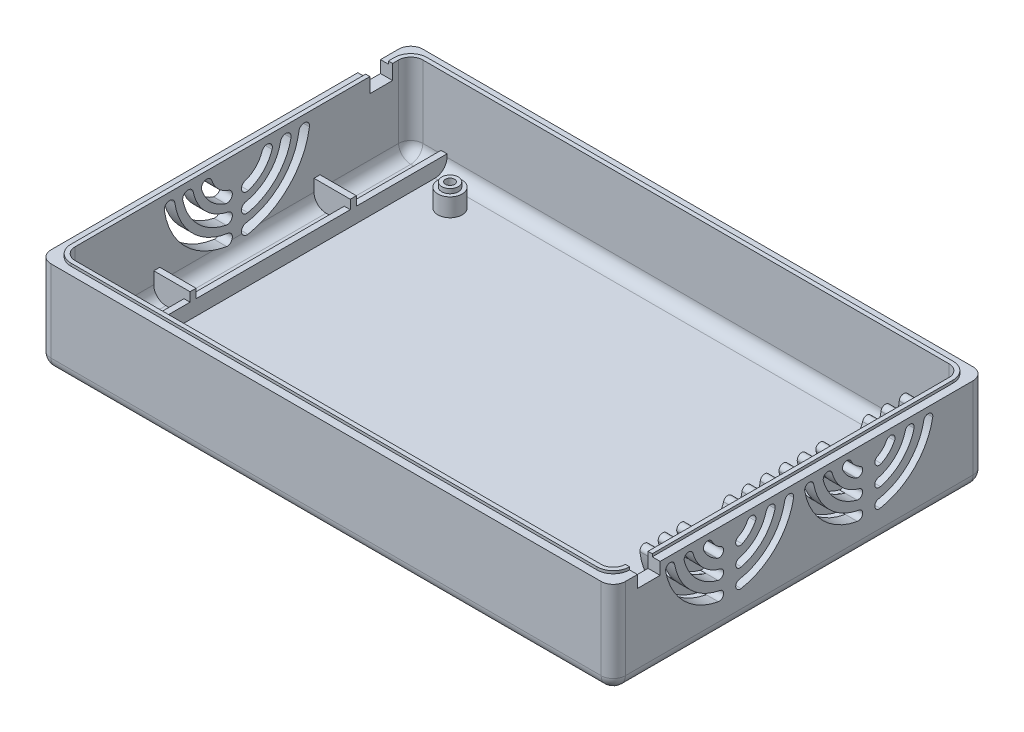
SolidWorks part; units mm, degrees
ref_plane "Front Plane" through (0, 0, 0) normal (0, 0, 1) x (1, 0, 0)
ref_plane "Top Plane" through (0, 0, 0) normal (0, 1, 0) x (1, 0, 0)
ref_plane "Right Plane" through (0, 0, 0) normal (1, 0, 0) x (0, 0, -1)
sketch "Sketch1" plane through (0, 0, 0) normal (0, 1, 0) x (1, 0, 0)
  line L1 (-73.5, -47.5) -> (73.5, -47.5) construction
  line L2 (-73.5, -47.5) -> (-73.5, 47.5) construction
  line L3 (-73.5, 47.5) -> (73.5, 47.5) construction
  line L4 (73.5, -47.5) -> (73.5, 47.5) construction
  line L5 (-73.5, -47.5) -> (73.5, 47.5) construction
  line L6 (-73.5, 47.5) -> (73.5, -47.5) construction
  line L7 (-80.5, -55.5) -> (80.5, -55.5) construction
  line L8 (-80.5, -55.5) -> (-80.5, 55.5) construction
  line L9 (-80.5, 55.5) -> (80.5, 55.5) construction
  line L10 (80.5, -55.5) -> (80.5, 55.5) construction
  line L11 (-80.5, -55.5) -> (80.5, 55.5) construction
  line L12 (-80.5, 55.5) -> (80.5, -55.5) construction
  line L13 (-100.5, 61.5) -> (89.5, 61.5)
  line L14 (-100.5, 61.5) -> (-100.5, -61.5)
  line L15 (-100.5, -61.5) -> (89.5, -61.5)
  line L16 (89.5, 61.5) -> (89.5, -61.5)
  circle A0 centre (73.5, -47.5) radius 1.5
  circle A1 centre (73.5, 47.5) radius 1.5
  circle A2 centre (-73.5, 47.5) radius 1.5
  circle A3 centre (-73.5, -47.5) radius 1.5
  point P0 (0, 0)
  point P6 (0, 0)
  dimension "D9" = 3
  dimension "D1" = 147
  dimension "D2" = 95
  dimension "D3" = 111
  dimension "D4" = 9
  dimension "D5" = 20
  dimension "D6" = 6
  dimension "D7" = 6
  dimension "D8" = 161
extrude "Boss-Extrude1" add sketch "Sketch1" along normal blind 4
sketch "Sketch3" plane through (0, 4, 0) normal (0, 1, 0) x (1, 0, 0)
  circle A0 centre (-73.5, 47.5) radius 4
  circle A1 centre (-73.5, -47.5) radius 4
  circle A2 centre (73.5, -47.5) radius 4
  circle A3 centre (73.5, 47.5) radius 4
  circle A4 centre (-73.5, 47.5) radius 1.5 construction
  circle A5 centre (-73.5, -47.5) radius 1.5 construction
  circle A6 centre (73.5, -47.5) radius 1.5 construction
  circle A7 centre (73.5, 47.5) radius 1.5 construction
  circle A8 centre (-73.5, 47.5) radius 1.5
  circle A9 centre (-73.5, -47.5) radius 1.5
  circle A10 centre (73.5, -47.5) radius 1.5
  circle A11 centre (73.5, 47.5) radius 1.5
  dimension "D1" = 8
extrude "Boss-Extrude3" add sketch "Sketch3" along normal blind 6
sketch "Sketch4" plane through (0, 10, 0) normal (0, 1, 0) x (1, 0, 0)
  circle A0 centre (73.5, -47.5) radius 1.5 construction
  circle A1 centre (73.5, 47.5) radius 1.5 construction
  circle A2 centre (-73.5, 47.5) radius 1.5 construction
  circle A3 centre (-73.5, -47.5) radius 1.5 construction
  circle A4 centre (73.5, -47.5) radius 1.5
  circle A5 centre (73.5, 47.5) radius 1.5
  circle A6 centre (-73.5, 47.5) radius 1.5
  circle A7 centre (-73.5, -47.5) radius 1.5
  circle A8 centre (-73.5, 47.5) radius 2.75
  circle A9 centre (73.5, 47.5) radius 2.75
  circle A10 centre (73.5, -47.5) radius 2.75
  circle A11 centre (-73.5, -47.5) radius 2.75
  dimension "D1" = 5.5
extrude "Boss-Extrude4" add sketch "Sketch4" along normal blind 1.5
sketch "Sketch2" plane through (0, 4, 0) normal (0, 1, 0) x (1, 0, 0)
  line L0 (-96.5, 57.5) -> (-96.5, -57.5)
  line L1 (-96.5, -57.5) -> (85.5, -57.5)
  line L2 (85.5, -57.5) -> (85.5, 57.5)
  line L3 (85.5, 57.5) -> (-96.5, 57.5)
  line L4 (-100.5, 61.5) -> (-100.5, -61.5)
  line L5 (-100.5, -61.5) -> (89.5, -61.5)
  line L6 (89.5, -61.5) -> (89.5, 61.5)
  line L7 (89.5, 61.5) -> (-100.5, 61.5)
  line L8 (-100.5, 61.5) -> (-100.5, -61.5)
  line L9 (-100.5, -61.5) -> (89.5, -61.5)
  line L10 (89.5, -61.5) -> (89.5, 61.5)
  line L11 (89.5, 61.5) -> (-100.5, 61.5)
  dimension "D1" = 0
  dimension "D2" = 4
extrude "Boss-Extrude2" add sketch "Sketch2" along normal blind 27
fillet "Fillet1" radius 4 8 edges at (-96.5, 17.5, 57.5) (-96.5, 17.5, -57.5) (85.5, 17.5, -57.5) (85.5, 17.5, 57.5) (85.5, 4, 0) (-5.5, 4, 57.5) (-96.5, 4, 0) (-5.5, 4, -57.5)
fillet "Fillet2" radius 4 8 edges at (89.5, 15.5, -61.5) (89.5, 0, 0) (89.5, 15.5, 61.5) (-5.5, 0, -61.5) (-100.5, 15.5, -61.5) (-100.5, 15.5, 61.5) (-5.5, 0, 61.5) (-100.5, 0, 0)
sketch "Sketch6" plane through (0, 0, 0) normal (0, -1, 0) x (1, 0, 0)
  circle A0 centre (73.5, 47.5) radius 6
  circle A1 centre (-73.5, 47.5) radius 6
  circle A2 centre (-73.5, -47.5) radius 6
  circle A3 centre (73.5, -47.5) radius 6
  circle A4 centre (73.5, 47.5) radius 1.5 construction
  circle A5 centre (73.5, -47.5) radius 1.5 construction
  circle A6 centre (-73.5, -47.5) radius 1.5 construction
  circle A7 centre (-73.5, 47.5) radius 1.5 construction
  circle A8 centre (73.5, 47.5) radius 1.5
  circle A9 centre (73.5, -47.5) radius 1.5
  circle A10 centre (-73.5, -47.5) radius 1.5
  circle A11 centre (-73.5, 47.5) radius 1.5
  circle A12 centre (-73.5, 47.5) radius 3
  circle A13 centre (73.5, 47.5) radius 3
  circle A14 centre (73.5, -47.5) radius 3
  circle A15 centre (-73.5, -47.5) radius 3
  dimension "D1" = 12
  dimension "D2" = 6
extrude "Boss-Extrude5" add sketch "Sketch6" along normal blind 4 contours A1 A12 | A2 A15 | A3 A14 | A0 A13 region at (67.6697, 0, 47.5) region at (-79.3303, 0, 47.5) region at (-79.3303, 0, -47.5) region at (67.6697, 0, -47.5)
fillet "Fillet3" radius 2 8 edges at (73.5, 0, 53.5) (73.5, 0, -41.5) (-73.5, 0, 53.5) (-73.5, 0, -41.5) (-73.5, -4, -53.5) (-73.5, -4, 41.5) (73.5, -4, 41.5) (73.5, -4, -53.5)
sketch "Sketch7" plane through (0, 4, 0) normal (0, 1, 0) x (1, 0, 0)
  line L0 (81.5, 57.5) -> (-92.5, 57.5) construction
  line L1 (-86.5, 57.5) -> (-84.5, 57.5)
  line L2 (-86.5, 57.5) -> (-86.5, -57.5)
  line L3 (-86.5, -57.5) -> (-84.5, -57.5)
  line L4 (-84.5, 57.5) -> (-84.5, -57.5)
  line L5 (81.5, -57.5) -> (-92.5, -57.5) construction
  line L6 (-96.5, -53.5) -> (-96.5, 53.5) construction
  dimension "D1" = 2
  dimension "D2" = 10
extrude "Boss-Extrude6" add sketch "Sketch7" along normal blind 5
sketch "Sketch8" plane through (0, 31, 0) normal (0, 1, 0) x (1, 0, 0)
  line L0 (-100.5, 57.5) -> (-100.5, -57.5) construction
  line L1 (-100.5, 51.5) -> (-96.5, 51.5)
  line L2 (-100.5, 51.5) -> (-100.5, 44)
  line L3 (-100.5, 44) -> (-96.5, 44)
  line L4 (-96.5, 51.5) -> (-96.5, 44)
  line L5 (-96.5, -53.5) -> (-96.5, 53.5) construction
  line L6 (85.5, 61.5) -> (-96.5, 61.5) construction
  line L7 (85.5, 53.5) -> (85.5, -53.5) construction
  line L8 (85.5, -46) -> (89.5, -46)
  line L9 (85.5, -46) -> (85.5, -53.5)
  line L10 (85.5, -53.5) -> (89.5, -53.5)
  line L11 (89.5, -46) -> (89.5, -53.5)
  line L12 (89.5, -57.5) -> (89.5, 57.5) construction
  line L13 (-96.5, -61.5) -> (85.5, -61.5) construction
  dimension "D1" = 7.5
  dimension "D2" = 10
  dimension "D3" = 8
  dimension "D4" = 7.5
extrude "Cut-Extrude1" cut sketch "Sketch8" against normal blind 4
sketch "Sketch9" plane through (-100.5, 0, 0) normal (-1, 0, 0) x (0, 0, 1)
  line L0 (-25, 31) -> (25, 31) construction
  line L1 (25, 6) -> (-25, 6)
  line L2 (25, 6) -> (25, 56)
  line L3 (25, 56) -> (-25, 56)
  line L4 (-25, 6) -> (-25, 56)
  line L5 (-44, 31) -> (57.5, 31) construction
  line L6 (0, 0) -> (0, 6)
  line L7 (0, 53.5) -> (0, 8.5) construction
  circle A0 centre (0, 31) radius 22.5 construction
  circle A1 centre (0, 31) radius 16.5 construction
  circle A2 centre (0, 31) radius 10.5 construction
  arc A3 (-3.25, 8.736) -> (-22.264, 27.75) centre (0, 31) cw construction
  arc A4 (-23.9957, 27.4972) -> (-3.5028, 7.0043) centre (0, 31) ccw
  arc A5 (-20.5324, 28.0028) -> (-2.9972, 10.4676) centre (0, 31) ccw
  arc A6 (-20.5324, 28.0028) -> (-23.9957, 27.4972) centre (-22.264, 27.75) ccw
  arc A7 (-3.5028, 7.0043) -> (-2.9972, 10.4676) centre (-3.25, 8.736) ccw
  arc A8 (22.264, 27.75) -> (3.25, 8.736) centre (0, 31) cw construction
  arc A9 (3.5028, 7.0043) -> (23.9957, 27.4972) centre (0, 31) ccw
  arc A10 (2.9972, 10.4676) -> (20.5324, 28.0028) centre (0, 31) ccw
  arc A11 (2.9972, 10.4676) -> (3.5028, 7.0043) centre (3.25, 8.736) ccw
  arc A12 (23.9957, 27.4972) -> (20.5324, 28.0028) centre (22.264, 27.75) ccw
  arc A13 (-3.25, 14.8232) -> (-16.1768, 27.75) centre (0, 31) cw construction
  arc A14 (-17.8925, 27.4053) -> (-3.5947, 13.1075) centre (0, 31) ccw
  arc A15 (-14.461, 28.0947) -> (-2.9053, 16.539) centre (0, 31) ccw
  arc A16 (-14.461, 28.0947) -> (-17.8925, 27.4053) centre (-16.1768, 27.75) ccw
  arc A17 (-3.5947, 13.1075) -> (-2.9053, 16.539) centre (-3.25, 14.8232) ccw
  arc A18 (-3.25, 21.0156) -> (-9.9844, 27.75) centre (0, 31) cw construction
  arc A19 (-11.6484, 27.2083) -> (-3.7917, 19.3516) centre (0, 31) ccw
  arc A20 (-8.3203, 28.2917) -> (-2.7083, 22.6797) centre (0, 31) ccw
  arc A21 (-8.3203, 28.2917) -> (-11.6484, 27.2083) centre (-9.9844, 27.75) ccw
  arc A22 (-3.7917, 19.3516) -> (-2.7083, 22.6797) centre (-3.25, 21.0156) ccw
  arc A23 (3.25, 21.0156) -> (9.9844, 27.75) centre (0, 31) ccw construction
  arc A24 (3.7917, 19.3516) -> (11.6484, 27.2083) centre (0, 31) ccw
  arc A25 (2.7083, 22.6797) -> (8.3203, 28.2917) centre (0, 31) ccw
  arc A26 (2.7083, 22.6797) -> (3.7917, 19.3516) centre (3.25, 21.0156) ccw
  arc A27 (11.6484, 27.2083) -> (8.3203, 28.2917) centre (9.9844, 27.75) ccw
  arc A28 (3.25, 14.8232) -> (16.1768, 27.75) centre (0, 31) ccw construction
  arc A29 (3.5947, 13.1075) -> (17.8925, 27.4053) centre (0, 31) ccw
  arc A30 (2.9053, 16.539) -> (14.461, 28.0947) centre (0, 31) ccw
  arc A31 (2.9053, 16.539) -> (3.5947, 13.1075) centre (3.25, 14.8232) ccw
  arc A32 (17.8925, 27.4053) -> (14.461, 28.0947) centre (16.1768, 27.75) ccw
  arc A33 (-3.25, 53.264) -> (-22.264, 34.25) centre (0, 31) ccw construction
  arc A34 (-23.9957, 34.5028) -> (-3.5028, 54.9957) centre (0, 31) cw
  arc A35 (-20.5324, 33.9972) -> (-2.9972, 51.5324) centre (0, 31) cw
  arc A36 (-20.5324, 33.9972) -> (-23.9957, 34.5028) centre (-22.264, 34.25) cw
  arc A37 (-3.5028, 54.9957) -> (-2.9972, 51.5324) centre (-3.25, 53.264) cw
  arc A38 (22.264, 34.25) -> (3.25, 53.264) centre (0, 31) ccw construction
  arc A39 (3.5028, 54.9957) -> (23.9957, 34.5028) centre (0, 31) cw
  arc A40 (2.9972, 51.5324) -> (20.5324, 33.9972) centre (0, 31) cw
  arc A41 (2.9972, 51.5324) -> (3.5028, 54.9957) centre (3.25, 53.264) cw
  arc A42 (23.9957, 34.5028) -> (20.5324, 33.9972) centre (22.264, 34.25) cw
  arc A43 (-3.25, 47.1768) -> (-16.1768, 34.25) centre (0, 31) ccw construction
  arc A44 (-17.8925, 34.5947) -> (-3.5947, 48.8925) centre (0, 31) cw
  arc A45 (-14.461, 33.9053) -> (-2.9053, 45.461) centre (0, 31) cw
  arc A46 (-14.461, 33.9053) -> (-17.8925, 34.5947) centre (-16.1768, 34.25) cw
  arc A47 (-3.5947, 48.8925) -> (-2.9053, 45.461) centre (-3.25, 47.1768) cw
  arc A48 (-3.25, 40.9844) -> (-9.9844, 34.25) centre (0, 31) ccw construction
  arc A49 (-11.6484, 34.7917) -> (-3.7917, 42.6484) centre (0, 31) cw
  arc A50 (-8.3203, 33.7083) -> (-2.7083, 39.3203) centre (0, 31) cw
  arc A51 (-8.3203, 33.7083) -> (-11.6484, 34.7917) centre (-9.9844, 34.25) cw
  arc A52 (-3.7917, 42.6484) -> (-2.7083, 39.3203) centre (-3.25, 40.9844) cw
  arc A53 (3.25, 40.9844) -> (9.9844, 34.25) centre (0, 31) cw construction
  arc A54 (3.7917, 42.6484) -> (11.6484, 34.7917) centre (0, 31) cw
  arc A55 (2.7083, 39.3203) -> (8.3203, 33.7083) centre (0, 31) cw
  arc A56 (2.7083, 39.3203) -> (3.7917, 42.6484) centre (3.25, 40.9844) cw
  arc A57 (11.6484, 34.7917) -> (8.3203, 33.7083) centre (9.9844, 34.25) cw
  arc A58 (3.25, 47.1768) -> (16.1768, 34.25) centre (0, 31) cw construction
  arc A59 (3.5947, 48.8925) -> (17.8925, 34.5947) centre (0, 31) cw
  arc A60 (2.9053, 45.461) -> (14.461, 33.9053) centre (0, 31) cw
  arc A61 (2.9053, 45.461) -> (3.5947, 48.8925) centre (3.25, 47.1768) cw
  arc A62 (17.8925, 34.5947) -> (14.461, 33.9053) centre (16.1768, 34.25) cw
  point P19 (-15.9099, 15.0901)
  point P24 (15.9099, 15.0901)
  point P35 (-11.6673, 19.3327)
  point P43 (-7.4246, 23.5754)
  point P51 (7.4246, 23.5754)
  point P59 (11.6673, 19.3327)
  point P64 (0, 0)
  point P65 (0, 0)
  point P66 (0, 0)
  point P67 (0, 0)
  point P68 (0, 0)
  point P69 (15.5265, 25.4163)
  point P70 (0, 0)
  point P71 (22.2891, 27.6475)
  point P72 (0, 0)
  point P75 (-15.9099, 46.9099)
  point P82 (15.9099, 46.9099)
  point P89 (-11.6673, 42.6673)
  point P96 (-7.4246, 38.4246)
  point P103 (7.4246, 38.4246)
  point P110 (11.6673, 42.6673)
  dimension "D2" = 45
  dimension "D3" = 6
  dimension "D4" = 6
  dimension "D5" = 3.5
  dimension "D6" = 1.5
  dimension "D7" = 1.5
  dimension "D1" = 50
extrude "Cut-Extrude2" cut sketch "Sketch9" against normal blind 10 contours A19 A22 A20 A21 | A14 A17 A15 A16 | A4 A7 A5 A6 | A9 A12 A10 A11 | A24 A27 A25 A26 | A29 A32 A30 A31 region at (-100.5, 29.1666, -22.4708) region at (-100.5, 8.5292, 1.8334) region at (-100.5, 20.1525, -10.8475) region at (-100.5, 23.9632, -7.0368) region at (-100.5, 23.9632, 7.0368)
sketch "Sketch10" plane through (89.5, 0, 0) normal (1, 0, 0) x (0, 0, -1)
  line L0 (-46, 31) -> (57.5, 31) construction
  line L5 (23, 51) -> (23, 11) construction
  line L6 (3, 31) -> (43, 31) construction
  circle A0 centre (23, 31) radius 20 construction
  circle A2 centre (23, 31) radius 14 construction
  arc A3 (3.3086, 27.5) -> (19.5, 11.3086) centre (23, 31) ccw construction
  arc A4 (1.8318, 27.2375) -> (19.2375, 9.8318) centre (23, 31) ccw
  arc A5 (4.7855, 27.7625) -> (19.7625, 12.7855) centre (23, 31) ccw
  arc A6 (4.7855, 27.7625) -> (1.8318, 27.2375) centre (3.3086, 27.5) ccw
  arc A7 (19.2375, 9.8318) -> (19.7625, 12.7855) centre (19.5, 11.3086) ccw
  arc A8 (9.4446, 27.5) -> (19.5, 17.4446) centre (23, 31) ccw construction
  arc A9 (7.9922, 27.125) -> (19.125, 15.9922) centre (23, 31) ccw
  arc A10 (10.8969, 27.875) -> (19.875, 18.8969) centre (23, 31) ccw
  arc A11 (10.8969, 27.875) -> (7.9922, 27.125) centre (9.4446, 27.5) ccw
  arc A12 (19.125, 15.9922) -> (19.875, 18.8969) centre (19.5, 17.4446) ccw
  circle A13 centre (23, 31) radius 8 construction
  arc A14 (19.5, 23.8063) -> (15.8063, 27.5) centre (23, 31) cw construction
  arc A15 (14.4574, 26.8437) -> (18.8437, 22.4574) centre (23, 31) ccw
  arc A16 (17.1551, 28.1562) -> (20.1562, 25.1551) centre (23, 31) ccw
  arc A17 (17.1551, 28.1562) -> (14.4574, 26.8437) centre (15.8063, 27.5) ccw
  arc A18 (18.8437, 22.4574) -> (20.1562, 25.1551) centre (19.5, 23.8063) ccw
  arc A19 (42.6914, 27.5) -> (26.5, 11.3086) centre (23, 31) cw construction
  arc A20 (44.1682, 27.2375) -> (26.7625, 9.8318) centre (23, 31) cw
  arc A21 (41.2145, 27.7625) -> (26.2375, 12.7855) centre (23, 31) cw
  arc A22 (41.2145, 27.7625) -> (44.1682, 27.2375) centre (42.6914, 27.5) cw
  arc A23 (26.7625, 9.8318) -> (26.2375, 12.7855) centre (26.5, 11.3086) cw
  arc A24 (36.5554, 27.5) -> (26.5, 17.4446) centre (23, 31) cw construction
  arc A25 (38.0078, 27.125) -> (26.875, 15.9922) centre (23, 31) cw
  arc A26 (35.1031, 27.875) -> (26.125, 18.8969) centre (23, 31) cw
  arc A27 (35.1031, 27.875) -> (38.0078, 27.125) centre (36.5554, 27.5) cw
  arc A28 (26.875, 15.9922) -> (26.125, 18.8969) centre (26.5, 17.4446) cw
  arc A29 (26.5, 23.8063) -> (30.1937, 27.5) centre (23, 31) ccw construction
  arc A30 (31.5426, 26.8438) -> (27.1563, 22.4574) centre (23, 31) cw
  arc A31 (28.8449, 28.1562) -> (25.8438, 25.1551) centre (23, 31) cw
  arc A32 (28.8449, 28.1562) -> (31.5426, 26.8438) centre (30.1937, 27.5) cw
  arc A33 (27.1563, 22.4574) -> (25.8438, 25.1551) centre (26.5, 23.8063) cw
  arc A34 (3.3086, 34.5) -> (19.5, 50.6914) centre (23, 31) cw construction
  arc A35 (1.8318, 34.7625) -> (19.2375, 52.1682) centre (23, 31) cw
  arc A36 (4.7855, 34.2375) -> (19.7625, 49.2145) centre (23, 31) cw
  arc A37 (4.7855, 34.2375) -> (1.8318, 34.7625) centre (3.3086, 34.5) cw
  arc A38 (19.2375, 52.1682) -> (19.7625, 49.2145) centre (19.5, 50.6914) cw
  arc A39 (9.4446, 34.5) -> (19.5, 44.5554) centre (23, 31) cw construction
  arc A40 (7.9922, 34.875) -> (19.125, 46.0078) centre (23, 31) cw
  arc A41 (10.8969, 34.125) -> (19.875, 43.1031) centre (23, 31) cw
  arc A42 (10.8969, 34.125) -> (7.9922, 34.875) centre (9.4446, 34.5) cw
  arc A43 (19.125, 46.0078) -> (19.875, 43.1031) centre (19.5, 44.5554) cw
  arc A44 (19.5, 38.1937) -> (15.8063, 34.5) centre (23, 31) ccw construction
  arc A45 (14.4574, 35.1563) -> (18.8437, 39.5426) centre (23, 31) cw
  arc A46 (17.1551, 33.8438) -> (20.1562, 36.8449) centre (23, 31) cw
  arc A47 (17.1551, 33.8438) -> (14.4574, 35.1563) centre (15.8063, 34.5) cw
  arc A48 (18.8437, 39.5426) -> (20.1562, 36.8449) centre (19.5, 38.1937) cw
  arc A49 (42.6914, 34.5) -> (26.5, 50.6914) centre (23, 31) ccw construction
  arc A50 (44.1682, 34.7625) -> (26.7625, 52.1682) centre (23, 31) ccw
  arc A51 (41.2145, 34.2375) -> (26.2375, 49.2145) centre (23, 31) ccw
  arc A52 (41.2145, 34.2375) -> (44.1682, 34.7625) centre (42.6914, 34.5) ccw
  arc A53 (26.7625, 52.1682) -> (26.2375, 49.2145) centre (26.5, 50.6914) ccw
  arc A54 (36.5554, 34.5) -> (26.5, 44.5554) centre (23, 31) ccw construction
  arc A55 (38.0078, 34.875) -> (26.875, 46.0078) centre (23, 31) ccw
  arc A56 (35.1031, 34.125) -> (26.125, 43.1031) centre (23, 31) ccw
  arc A57 (35.1031, 34.125) -> (38.0078, 34.875) centre (36.5554, 34.5) ccw
  arc A58 (26.875, 46.0078) -> (26.125, 43.1031) centre (26.5, 44.5554) ccw
  arc A59 (26.5, 38.1937) -> (30.1937, 34.5) centre (23, 31) cw construction
  arc A60 (31.5426, 35.1562) -> (27.1563, 39.5426) centre (23, 31) ccw
  arc A61 (28.8449, 33.8438) -> (25.8438, 36.8449) centre (23, 31) ccw
  arc A62 (28.8449, 33.8438) -> (31.5426, 35.1562) centre (30.1937, 34.5) ccw
  arc A63 (27.1563, 39.5426) -> (25.8438, 36.8449) centre (26.5, 38.1937) ccw
  point P11 (8.8579, 16.8579)
  point P16 (13.1005, 21.1005)
  point P28 (17.3431, 25.3431)
  point P33 (0, 0)
  point P34 (0, 0)
  point P35 (23.9599, 17.8489)
  point P36 (0, 0)
  point P39 (37.1421, 16.8579)
  point P46 (32.8995, 21.1005)
  point P53 (28.6569, 25.3431)
  point P61 (8.8579, 45.1421)
  point P68 (13.1005, 40.8995)
  point P75 (17.3431, 36.6569)
  point P82 (37.1421, 45.1421)
  point P89 (32.8995, 40.8995)
  point P96 (28.6569, 36.6569)
  dimension "D1" = 40
  dimension "D2" = 6
  dimension "D3" = 3
  dimension "D4" = 6
  dimension "D6" = 2
  dimension "D5" = 2
  dimension "D7" = 23
extrude "Cut-Extrude4" cut sketch "Sketch10" against normal blind 10
sketch "Sketch11" plane through (85.5, 0, 0) normal (-1, 0, 0) x (0, 0, 1)
  line L0 (-23, 51) -> (-23, 11) construction
  line L1 (-3, 31) -> (-43, 31) construction
  line L2 (-23, 51) -> (-23, 11) construction
  line L3 (-3, 31) -> (-43, 31) construction
  circle A0 centre (-23, 31) radius 20 construction
  circle A1 centre (-23, 31) radius 14 construction
  circle A2 centre (-23, 31) radius 8 construction
  circle A3 centre (-23, 31) radius 20 construction
  arc A4 (-19.2375, 9.8318) -> (-1.8318, 27.2375) centre (-23, 31) ccw
  arc A5 (-19.7625, 12.7855) -> (-19.2375, 9.8318) centre (-19.5, 11.3086) ccw
  arc A6 (-19.7625, 12.7855) -> (-4.7855, 27.7625) centre (-23, 31) ccw
  arc A7 (-1.8318, 27.2375) -> (-4.7855, 27.7625) centre (-3.3086, 27.5) ccw
  arc A8 (-19.2375, 9.8318) -> (-1.8318, 27.2375) centre (-23, 31) ccw
  arc A9 (-19.7625, 12.7855) -> (-19.2375, 9.8318) centre (-19.5, 11.3086) ccw
  arc A10 (-19.7625, 12.7855) -> (-4.7855, 27.7625) centre (-23, 31) ccw
  arc A11 (-1.8318, 27.2375) -> (-4.7855, 27.7625) centre (-3.3086, 27.5) ccw
  arc A12 (-19.125, 15.9922) -> (-7.9922, 27.125) centre (-23, 31) ccw
  arc A13 (-19.875, 18.8969) -> (-19.125, 15.9922) centre (-19.5, 17.4446) ccw
  arc A14 (-19.875, 18.8969) -> (-10.8969, 27.875) centre (-23, 31) ccw
  arc A15 (-7.9922, 27.125) -> (-10.8969, 27.875) centre (-9.4446, 27.5) ccw
  arc A16 (-19.125, 15.9922) -> (-7.9922, 27.125) centre (-23, 31) ccw
  arc A17 (-19.875, 18.8969) -> (-19.125, 15.9922) centre (-19.5, 17.4446) ccw
  arc A18 (-19.875, 18.8969) -> (-10.8969, 27.875) centre (-23, 31) ccw
  arc A19 (-7.9922, 27.125) -> (-10.8969, 27.875) centre (-9.4446, 27.5) ccw
  arc A20 (-44.1682, 27.2375) -> (-26.7625, 9.8318) centre (-23, 31) ccw
  arc A21 (-26.7625, 9.8318) -> (-26.2375, 12.7855) centre (-26.5, 11.3086) ccw
  arc A22 (-41.2145, 27.7625) -> (-26.2375, 12.7855) centre (-23, 31) ccw
  arc A23 (-41.2145, 27.7625) -> (-44.1682, 27.2375) centre (-42.6914, 27.5) ccw
  arc A24 (-44.1682, 27.2375) -> (-26.7625, 9.8318) centre (-23, 31) ccw
  arc A25 (-26.7625, 9.8318) -> (-26.2375, 12.7855) centre (-26.5, 11.3086) ccw
  arc A26 (-41.2145, 27.7625) -> (-26.2375, 12.7855) centre (-23, 31) ccw
  arc A27 (-41.2145, 27.7625) -> (-44.1682, 27.2375) centre (-42.6914, 27.5) ccw
  arc A28 (-20.1563, 25.1551) -> (-18.8438, 22.4574) centre (-19.5, 23.8063) ccw
  arc A29 (-18.8438, 22.4574) -> (-14.4574, 26.8437) centre (-23, 31) ccw
  arc A30 (-14.4574, 26.8437) -> (-17.1551, 28.1562) centre (-15.8063, 27.5) ccw
  arc A31 (-20.1563, 25.1551) -> (-17.1551, 28.1562) centre (-23, 31) ccw
  arc A32 (-20.1563, 25.1551) -> (-18.8438, 22.4574) centre (-19.5, 23.8063) ccw
  arc A33 (-18.8438, 22.4574) -> (-14.4574, 26.8437) centre (-23, 31) ccw
  arc A34 (-14.4574, 26.8437) -> (-17.1551, 28.1562) centre (-15.8063, 27.5) ccw
  arc A35 (-20.1563, 25.1551) -> (-17.1551, 28.1562) centre (-23, 31) ccw
  arc A36 (-31.5426, 26.8438) -> (-27.1563, 22.4574) centre (-23, 31) ccw
  arc A37 (-27.1563, 22.4574) -> (-25.8438, 25.1551) centre (-26.5, 23.8063) ccw
  arc A38 (-28.8449, 28.1562) -> (-25.8438, 25.1551) centre (-23, 31) ccw
  arc A39 (-28.8449, 28.1562) -> (-31.5426, 26.8438) centre (-30.1937, 27.5) ccw
  arc A40 (-31.5426, 26.8438) -> (-27.1563, 22.4574) centre (-23, 31) ccw
  arc A41 (-27.1563, 22.4574) -> (-25.8438, 25.1551) centre (-26.5, 23.8063) ccw
  arc A42 (-28.8449, 28.1562) -> (-25.8438, 25.1551) centre (-23, 31) ccw
  arc A43 (-28.8449, 28.1562) -> (-31.5426, 26.8438) centre (-30.1937, 27.5) ccw
  arc A44 (-26.875, 15.9922) -> (-26.125, 18.8969) centre (-26.5, 17.4446) ccw
  arc A45 (-35.1031, 27.875) -> (-26.125, 18.8969) centre (-23, 31) ccw
  arc A46 (-35.1031, 27.875) -> (-38.0078, 27.125) centre (-36.5554, 27.5) ccw
  arc A47 (-38.0078, 27.125) -> (-26.875, 15.9922) centre (-23, 31) ccw
  arc A48 (-26.875, 15.9922) -> (-26.125, 18.8969) centre (-26.5, 17.4446) ccw
  arc A49 (-35.1031, 27.875) -> (-26.125, 18.8969) centre (-23, 31) ccw
  arc A50 (-35.1031, 27.875) -> (-38.0078, 27.125) centre (-36.5554, 27.5) ccw
  arc A51 (-38.0078, 27.125) -> (-26.875, 15.9922) centre (-23, 31) ccw
  circle A52 centre (-23, 31) radius 14 construction
  circle A53 centre (-23, 31) radius 8 construction
  arc A54 (-30.7207, 28.9044) -> (-25.0956, 23.2793) centre (-23, 31) ccw construction
  arc A55 (-32.1683, 28.5115) -> (-25.4885, 21.8317) centre (-23, 31) ccw
  arc A56 (-29.273, 29.2973) -> (-24.7027, 24.727) centre (-23, 31) ccw
  arc A57 (-29.273, 29.2973) -> (-32.1683, 28.5115) centre (-30.7207, 28.9044) ccw
  arc A58 (-25.4885, 21.8317) -> (-24.7027, 24.727) centre (-25.0956, 23.2793) ccw
  arc A59 (-36.8521, 28.9704) -> (-25.0296, 17.1479) centre (-23, 31) ccw construction
  arc A60 (-38.3363, 28.7529) -> (-25.2471, 15.6637) centre (-23, 31) ccw
  arc A61 (-35.3679, 29.1878) -> (-24.8122, 18.6321) centre (-23, 31) ccw
  arc A62 (-35.3679, 29.1878) -> (-38.3363, 28.7529) centre (-36.8521, 28.9704) ccw
  arc A63 (-25.2471, 15.6637) -> (-24.8122, 18.6321) centre (-25.0296, 17.1479) ccw
  arc A64 (-42.8983, 28.9857) -> (-25.0143, 11.1017) centre (-23, 31) ccw construction
  arc A65 (-44.3907, 28.8346) -> (-25.1654, 9.6093) centre (-23, 31) ccw
  arc A66 (-41.4059, 29.1367) -> (-24.8633, 12.5941) centre (-23, 31) ccw
  arc A67 (-41.4059, 29.1367) -> (-44.3907, 28.8346) centre (-42.8983, 28.9857) ccw
  arc A68 (-25.1654, 9.6093) -> (-24.8633, 12.5941) centre (-25.0143, 11.1017) ccw
  arc A69 (-15.2793, 28.9044) -> (-20.9044, 23.2793) centre (-23, 31) cw construction
  arc A70 (-13.8317, 28.5115) -> (-20.5115, 21.8317) centre (-23, 31) cw
  arc A71 (-16.727, 29.2973) -> (-21.2973, 24.727) centre (-23, 31) cw
  arc A72 (-16.727, 29.2973) -> (-13.8317, 28.5115) centre (-15.2793, 28.9044) cw
  arc A73 (-20.5115, 21.8317) -> (-21.2973, 24.727) centre (-20.9044, 23.2793) cw
  arc A74 (-9.1479, 28.9704) -> (-20.9704, 17.1479) centre (-23, 31) cw construction
  arc A75 (-7.6637, 28.7529) -> (-20.7529, 15.6637) centre (-23, 31) cw
  arc A76 (-10.6321, 29.1878) -> (-21.1878, 18.6321) centre (-23, 31) cw
  arc A77 (-10.6321, 29.1878) -> (-7.6637, 28.7529) centre (-9.1479, 28.9704) cw
  arc A78 (-20.7529, 15.6637) -> (-21.1878, 18.6321) centre (-20.9704, 17.1479) cw
  arc A79 (-3.1017, 28.9857) -> (-20.9857, 11.1017) centre (-23, 31) cw construction
  arc A80 (-1.6093, 28.8346) -> (-20.8346, 9.6093) centre (-23, 31) cw
  arc A81 (-4.5941, 29.1367) -> (-21.1367, 12.5941) centre (-23, 31) cw
  arc A82 (-4.5941, 29.1367) -> (-1.6093, 28.8346) centre (-3.1017, 28.9857) cw
  arc A83 (-20.8346, 9.6093) -> (-21.1367, 12.5941) centre (-20.9857, 11.1017) cw
  arc A84 (-7.9922, 27.125) -> (-19.125, 15.9922) centre (-23, 31) cw
  arc A85 (-10.8969, 27.875) -> (-7.9922, 27.125) centre (-9.4446, 27.5) cw
  arc A86 (-10.8969, 27.875) -> (-19.875, 18.8969) centre (-23, 31) cw
  arc A87 (-19.125, 15.9922) -> (-19.875, 18.8969) centre (-19.5, 17.4446) cw
  arc A88 (-17.1551, 28.1562) -> (-14.4574, 26.8437) centre (-15.8063, 27.5) cw
  arc A89 (-17.1551, 28.1562) -> (-20.1563, 25.1551) centre (-23, 31) cw
  arc A90 (-18.8438, 22.4574) -> (-20.1563, 25.1551) centre (-19.5, 23.8063) cw
  arc A91 (-14.4574, 26.8437) -> (-18.8438, 22.4574) centre (-23, 31) cw
  arc A92 (-4.7855, 27.7625) -> (-1.8318, 27.2375) centre (-3.3086, 27.5) cw
  arc A93 (-4.7855, 27.7625) -> (-19.7625, 12.7855) centre (-23, 31) cw
  arc A94 (-19.2375, 9.8318) -> (-19.7625, 12.7855) centre (-19.5, 11.3086) cw
  arc A95 (-1.8318, 27.2375) -> (-19.2375, 9.8318) centre (-23, 31) cw
  arc A96 (-30.7207, 33.0956) -> (-25.0956, 38.7207) centre (-23, 31) cw construction
  arc A97 (-32.1683, 33.4885) -> (-25.4885, 40.1683) centre (-23, 31) cw
  arc A98 (-29.273, 32.7027) -> (-24.7027, 37.273) centre (-23, 31) cw
  arc A99 (-29.273, 32.7027) -> (-32.1683, 33.4885) centre (-30.7207, 33.0956) cw
  arc A100 (-25.4885, 40.1683) -> (-24.7027, 37.273) centre (-25.0956, 38.7207) cw
  arc A101 (-36.8521, 33.0296) -> (-25.0296, 44.8521) centre (-23, 31) cw construction
  arc A102 (-38.3363, 33.2471) -> (-25.2471, 46.3363) centre (-23, 31) cw
  arc A103 (-35.3679, 32.8122) -> (-24.8122, 43.3679) centre (-23, 31) cw
  arc A104 (-35.3679, 32.8122) -> (-38.3363, 33.2471) centre (-36.8521, 33.0296) cw
  arc A105 (-25.2471, 46.3363) -> (-24.8122, 43.3679) centre (-25.0296, 44.8521) cw
  arc A106 (-42.8983, 33.0143) -> (-25.0143, 50.8983) centre (-23, 31) cw construction
  arc A107 (-44.3907, 33.1654) -> (-25.1654, 52.3907) centre (-23, 31) cw
  arc A108 (-41.4059, 32.8633) -> (-24.8633, 49.4059) centre (-23, 31) cw
  arc A109 (-41.4059, 32.8633) -> (-44.3907, 33.1654) centre (-42.8983, 33.0143) cw
  arc A110 (-25.1654, 52.3907) -> (-24.8633, 49.4059) centre (-25.0143, 50.8983) cw
  arc A111 (-15.2793, 33.0956) -> (-20.9044, 38.7207) centre (-23, 31) ccw construction
  arc A112 (-13.8317, 33.4885) -> (-20.5115, 40.1683) centre (-23, 31) ccw
  arc A113 (-16.727, 32.7027) -> (-21.2973, 37.273) centre (-23, 31) ccw
  arc A114 (-16.727, 32.7027) -> (-13.8317, 33.4885) centre (-15.2793, 33.0956) ccw
  arc A115 (-20.5115, 40.1683) -> (-21.2973, 37.273) centre (-20.9044, 38.7207) ccw
  arc A116 (-9.1479, 33.0296) -> (-20.9704, 44.8521) centre (-23, 31) ccw construction
  arc A117 (-7.6637, 33.2471) -> (-20.7529, 46.3363) centre (-23, 31) ccw
  arc A118 (-10.6321, 32.8122) -> (-21.1878, 43.3679) centre (-23, 31) ccw
  arc A119 (-10.6321, 32.8122) -> (-7.6637, 33.2471) centre (-9.1479, 33.0296) ccw
  arc A120 (-20.7529, 46.3363) -> (-21.1878, 43.3679) centre (-20.9704, 44.8521) ccw
  arc A121 (-3.1017, 33.0143) -> (-20.9857, 50.8983) centre (-23, 31) ccw construction
  arc A122 (-1.6093, 33.1654) -> (-20.8346, 52.3907) centre (-23, 31) ccw
  arc A123 (-4.5941, 32.8633) -> (-21.1367, 49.4059) centre (-23, 31) ccw
  arc A124 (-4.5941, 32.8633) -> (-1.6093, 33.1654) centre (-3.1017, 33.0143) ccw
  arc A125 (-20.8346, 52.3907) -> (-21.1367, 49.4059) centre (-20.9857, 50.8983) ccw
  arc A126 (-1.8318, 34.7625) -> (-19.2375, 52.1682) centre (-23, 31) ccw
  arc A127 (-19.2375, 52.1682) -> (-19.7625, 49.2145) centre (-19.5, 50.6914) ccw
  arc A128 (-4.7855, 34.2375) -> (-19.7625, 49.2145) centre (-23, 31) ccw
  arc A129 (-4.7855, 34.2375) -> (-1.8318, 34.7625) centre (-3.3086, 34.5) ccw
  arc A130 (-14.4574, 35.1563) -> (-18.8438, 39.5426) centre (-23, 31) ccw
  arc A131 (-18.8438, 39.5426) -> (-20.1563, 36.8449) centre (-19.5, 38.1937) ccw
  arc A132 (-17.1551, 33.8438) -> (-20.1563, 36.8449) centre (-23, 31) ccw
  arc A133 (-17.1551, 33.8438) -> (-14.4574, 35.1563) centre (-15.8063, 34.5) ccw
  arc A134 (-19.125, 46.0078) -> (-19.875, 43.1031) centre (-19.5, 44.5554) ccw
  arc A135 (-10.8969, 34.125) -> (-19.875, 43.1031) centre (-23, 31) ccw
  arc A136 (-10.8969, 34.125) -> (-7.9922, 34.875) centre (-9.4446, 34.5) ccw
  arc A137 (-7.9922, 34.875) -> (-19.125, 46.0078) centre (-23, 31) ccw
  arc A138 (-38.0078, 34.875) -> (-26.875, 46.0078) centre (-23, 31) cw
  arc A139 (-35.1031, 34.125) -> (-38.0078, 34.875) centre (-36.5554, 34.5) cw
  arc A140 (-35.1031, 34.125) -> (-26.125, 43.1031) centre (-23, 31) cw
  arc A141 (-26.875, 46.0078) -> (-26.125, 43.1031) centre (-26.5, 44.5554) cw
  arc A142 (-28.8449, 33.8438) -> (-31.5426, 35.1562) centre (-30.1937, 34.5) cw
  arc A143 (-28.8449, 33.8438) -> (-25.8438, 36.8449) centre (-23, 31) cw
  arc A144 (-27.1563, 39.5426) -> (-25.8438, 36.8449) centre (-26.5, 38.1937) cw
  arc A145 (-31.5426, 35.1562) -> (-27.1563, 39.5426) centre (-23, 31) cw
  arc A146 (-20.1563, 36.8449) -> (-17.1551, 33.8438) centre (-23, 31) cw
  arc A147 (-14.4574, 35.1563) -> (-17.1551, 33.8438) centre (-15.8063, 34.5) cw
  arc A148 (-18.8438, 39.5426) -> (-14.4574, 35.1563) centre (-23, 31) cw
  arc A149 (-20.1563, 36.8449) -> (-18.8438, 39.5426) centre (-19.5, 38.1937) cw
  arc A150 (-41.2145, 34.2375) -> (-44.1682, 34.7625) centre (-42.6914, 34.5) cw
  arc A151 (-41.2145, 34.2375) -> (-26.2375, 49.2145) centre (-23, 31) cw
  arc A152 (-26.7625, 52.1682) -> (-26.2375, 49.2145) centre (-26.5, 50.6914) cw
  arc A153 (-44.1682, 34.7625) -> (-26.7625, 52.1682) centre (-23, 31) cw
  arc A154 (-7.9922, 34.875) -> (-10.8969, 34.125) centre (-9.4446, 34.5) cw
  arc A155 (-19.875, 43.1031) -> (-10.8969, 34.125) centre (-23, 31) cw
  arc A156 (-19.875, 43.1031) -> (-19.125, 46.0078) centre (-19.5, 44.5554) cw
  arc A157 (-19.125, 46.0078) -> (-7.9922, 34.875) centre (-23, 31) cw
  arc A158 (-1.8318, 34.7625) -> (-4.7855, 34.2375) centre (-3.3086, 34.5) cw
  arc A159 (-19.7625, 49.2145) -> (-4.7855, 34.2375) centre (-23, 31) cw
  arc A160 (-19.7625, 49.2145) -> (-19.2375, 52.1682) centre (-19.5, 50.6914) cw
  arc A161 (-19.2375, 52.1682) -> (-1.8318, 34.7625) centre (-23, 31) cw
  point P60 (-28.6569, 25.3431)
  point P67 (-32.8995, 21.1005)
  point P74 (-37.1421, 16.8579)
  point P81 (-17.3431, 25.3431)
  point P88 (-13.1005, 21.1005)
  point P95 (-8.8579, 16.8579)
  point P102 (-28.6569, 36.6569)
  point P109 (-32.8995, 40.8995)
  point P116 (-37.1421, 45.1421)
  point P123 (-17.3431, 36.6569)
  point P130 (-13.1005, 40.8995)
  point P137 (-8.8579, 45.1421)
  arc M30 (-17.1551, 28.1562) -> (-14.4574, 26.8437) centre (-15.8063, 27.5) cw
  arc M32 (-18.8438, 22.4574) -> (-20.1563, 25.1551) centre (-19.5, 23.8063) cw
  arc M34 (-10.8969, 27.875) -> (-7.9922, 27.125) centre (-9.4446, 27.5) cw
  arc M36 (-19.125, 15.9922) -> (-19.875, 18.8969) centre (-19.5, 17.4446) cw
  arc M38 (-38.0078, 27.125) -> (-35.1031, 27.875) centre (-36.5554, 27.5) cw
  arc M40 (-26.125, 18.8969) -> (-26.875, 15.9922) centre (-26.5, 17.4446) cw
  arc M42 (-44.1682, 27.2375) -> (-41.2145, 27.7625) centre (-42.6914, 27.5) cw
  arc M44 (-26.2375, 12.7855) -> (-26.7625, 9.8318) centre (-26.5, 11.3086) cw
  arc M46 (-31.5426, 26.8438) -> (-28.8449, 28.1562) centre (-30.1937, 27.5) cw
  arc M48 (-25.8438, 25.1551) -> (-27.1563, 22.4574) centre (-26.5, 23.8063) cw
  arc M50 (-4.7855, 27.7625) -> (-1.8318, 27.2375) centre (-3.3086, 27.5) cw
  arc M52 (-19.2375, 9.8318) -> (-19.7625, 12.7855) centre (-19.5, 11.3086) cw
  dimension "D1" = 0
  dimension "D2" = 0
  dimension "D3" = 0
  dimension "D4" = 0
  dimension "D5" = 0
  dimension "D6" = 0
extrude "Boss-Extrude8" add sketch "Sketch11" along normal blind 1.8 contours A66 A67 A65 M42 | A61 A62 A60 M38 | A56 A57 A55 M46 | A55 A58 A56 M48 | A60 A63 A61 M40 | A65 A68 A66 M44 | A83 A80 A81 M52 | A78 A75 A76 M36 | A73 A70 A71 M32 | A72 A71 A70 M30 | A77 A76 A75 M34 | A82 A81 A80 M50 region at (85.5, 11.0334, -21.4081) region at (85.5, 29.4081, -3.0334) region at (85.5, 17.0502, -21.3868) region at (85.5, 29.3868, -9.0502) region at (85.5, 29.4081, -42.9666) region at (85.5, 11.0334, -24.5919) region at (85.5, 23.1076, -21.2954) region at (85.5, 29.2954, -15.1076) region at (85.5, 29.2954, -30.8924) region at (85.5, 23.1076, -24.7046) region at (85.5, 17.0502, -24.6132) region at (85.5, 29.3868, -36.9498)
sketch "Sketch12" plane through (83.7, 0, 0) normal (-1, 0, 0) x (0, 0, 1)
  line L0 (-44, 31) -> (57.5, 31) construction
  arc A0 (-19.875, 18.8969) -> (-10.8969, 27.875) centre (-23, 31) ccw construction
  arc A1 (-7.9922, 27.125) -> (-10.8969, 27.875) centre (-9.4446, 27.5) ccw construction
  arc A2 (-7.9922, 27.125) -> (-10.8969, 27.875) centre (-9.4446, 27.5) ccw construction
  arc A3 (-19.875, 18.8969) -> (-10.8969, 27.875) centre (-23, 31) ccw construction
  arc A4 (-19.875, 18.8969) -> (-19.125, 15.9922) centre (-19.5, 17.4446) ccw construction
  arc A5 (-19.875, 18.8969) -> (-19.125, 15.9922) centre (-19.5, 17.4446) ccw construction
  arc A6 (-19.125, 15.9922) -> (-7.9922, 27.125) centre (-23, 31) ccw construction
  arc A7 (-19.125, 15.9922) -> (-7.9922, 27.125) centre (-23, 31) ccw construction
  arc A8 (-19.7625, 12.7855) -> (-4.7855, 27.7625) centre (-23, 31) ccw construction
  arc A9 (-1.8318, 27.2375) -> (-4.7855, 27.7625) centre (-3.3086, 27.5) ccw construction
  arc A10 (-1.8318, 27.2375) -> (-4.7855, 27.7625) centre (-3.3086, 27.5) ccw construction
  arc A11 (-19.7625, 12.7855) -> (-4.7855, 27.7625) centre (-23, 31) ccw construction
  arc A12 (-19.7625, 12.7855) -> (-19.2375, 9.8318) centre (-19.5, 11.3086) ccw construction
  arc A13 (-19.7625, 12.7855) -> (-19.2375, 9.8318) centre (-19.5, 11.3086) ccw construction
  arc A14 (-19.2375, 9.8318) -> (-1.8318, 27.2375) centre (-23, 31) ccw construction
  arc A15 (-19.2375, 9.8318) -> (-1.8318, 27.2375) centre (-23, 31) ccw construction
  arc A16 (-14.4574, 26.8437) -> (-17.1551, 28.1562) centre (-15.8063, 27.5) ccw construction
  arc A17 (-20.1563, 25.1551) -> (-17.1551, 28.1562) centre (-23, 31) ccw construction
  arc A18 (-14.4574, 26.8437) -> (-17.1551, 28.1562) centre (-15.8063, 27.5) ccw construction
  arc A19 (-20.1563, 25.1551) -> (-17.1551, 28.1562) centre (-23, 31) ccw construction
  arc A20 (-18.8438, 22.4574) -> (-14.4574, 26.8437) centre (-23, 31) ccw construction
  arc A21 (-18.8438, 22.4574) -> (-14.4574, 26.8437) centre (-23, 31) ccw construction
  arc A22 (-20.1563, 25.1551) -> (-18.8438, 22.4574) centre (-19.5, 23.8063) ccw construction
  arc A23 (-20.1563, 25.1551) -> (-18.8438, 22.4574) centre (-19.5, 23.8063) ccw construction
  arc A24 (-26.7625, 9.8318) -> (-26.2375, 12.7855) centre (-26.5, 11.3086) ccw construction
  arc A25 (-41.2145, 27.7625) -> (-26.2375, 12.7855) centre (-23, 31) ccw construction
  arc A26 (-41.2145, 27.7625) -> (-44.1682, 27.2375) centre (-42.6914, 27.5) ccw construction
  arc A27 (-44.1682, 27.2375) -> (-26.7625, 9.8318) centre (-23, 31) ccw construction
  arc A28 (-26.875, 15.9922) -> (-26.125, 18.8969) centre (-26.5, 17.4446) ccw construction
  arc A29 (-35.1031, 27.875) -> (-26.125, 18.8969) centre (-23, 31) ccw construction
  arc A30 (-35.1031, 27.875) -> (-38.0078, 27.125) centre (-36.5554, 27.5) ccw construction
  arc A31 (-38.0078, 27.125) -> (-26.875, 15.9922) centre (-23, 31) ccw construction
  arc A32 (-27.1563, 22.4574) -> (-25.8438, 25.1551) centre (-26.5, 23.8063) ccw construction
  arc A33 (-28.8449, 28.1562) -> (-25.8438, 25.1551) centre (-23, 31) ccw construction
  arc A34 (-28.8449, 28.1562) -> (-31.5426, 26.8438) centre (-30.1937, 27.5) ccw construction
  arc A35 (-31.5426, 26.8438) -> (-27.1563, 22.4574) centre (-23, 31) ccw construction
  arc A36 (-44.3907, 28.8346) -> (-25.1654, 9.6093) centre (-23, 31) ccw construction
  arc A37 (-25.1654, 9.6093) -> (-24.8633, 12.5941) centre (-25.0143, 11.1017) ccw construction
  arc A38 (-41.4059, 29.1367) -> (-24.8633, 12.5941) centre (-23, 31) ccw construction
  arc A39 (-41.4059, 29.1367) -> (-44.3907, 28.8346) centre (-42.8983, 28.9857) ccw construction
  arc A40 (-38.3363, 28.7529) -> (-25.2471, 15.6637) centre (-23, 31) ccw construction
  arc A41 (-25.2471, 15.6637) -> (-24.8122, 18.6321) centre (-25.0296, 17.1479) ccw construction
  arc A42 (-35.3679, 29.1878) -> (-24.8122, 18.6321) centre (-23, 31) ccw construction
  arc A43 (-35.3679, 29.1878) -> (-38.3363, 28.7529) centre (-36.8521, 28.9704) ccw construction
  arc A44 (-25.4885, 21.8317) -> (-24.7027, 24.727) centre (-25.0956, 23.2793) ccw construction
  arc A45 (-32.1683, 28.5115) -> (-25.4885, 21.8317) centre (-23, 31) ccw construction
  arc A46 (-29.273, 29.2973) -> (-32.1683, 28.5115) centre (-30.7207, 28.9044) ccw construction
  arc A47 (-29.273, 29.2973) -> (-24.7027, 24.727) centre (-23, 31) ccw construction
  arc A48 (-20.7529, 15.6637) -> (-7.6637, 28.7529) centre (-23, 31) ccw construction
  arc A49 (-21.1878, 18.6321) -> (-20.7529, 15.6637) centre (-20.9704, 17.1479) ccw construction
  arc A50 (-21.1878, 18.6321) -> (-10.6321, 29.1878) centre (-23, 31) ccw construction
  arc A51 (-7.6637, 28.7529) -> (-10.6321, 29.1878) centre (-9.1479, 28.9704) ccw construction
  arc A52 (-20.5115, 21.8317) -> (-13.8317, 28.5115) centre (-23, 31) ccw construction
  arc A53 (-21.2973, 24.727) -> (-20.5115, 21.8317) centre (-20.9044, 23.2793) ccw construction
  arc A54 (-21.2973, 24.727) -> (-16.727, 29.2973) centre (-23, 31) ccw construction
  arc A55 (-13.8317, 28.5115) -> (-16.727, 29.2973) centre (-15.2793, 28.9044) ccw construction
  arc A56 (-20.8346, 9.6093) -> (-1.6093, 28.8346) centre (-23, 31) ccw construction
  arc A57 (-21.1367, 12.5941) -> (-20.8346, 9.6093) centre (-20.9857, 11.1017) ccw construction
  arc A58 (-21.1367, 12.5941) -> (-4.5941, 29.1367) centre (-23, 31) ccw construction
  arc A59 (-1.6093, 28.8346) -> (-4.5941, 29.1367) centre (-3.1017, 28.9857) ccw construction
  arc A60 (-19.875, 18.8969) -> (-10.8969, 27.875) centre (-23, 31) ccw
  arc A61 (-7.9922, 27.125) -> (-10.8969, 27.875) centre (-9.4446, 27.5) ccw construction
  arc A62 (-7.9922, 27.125) -> (-10.8969, 27.875) centre (-9.4446, 27.5) ccw
  arc A63 (-19.875, 18.8969) -> (-10.8969, 27.875) centre (-23, 31) ccw
  arc A64 (-19.875, 18.8969) -> (-19.125, 15.9922) centre (-19.5, 17.4446) ccw construction
  arc A65 (-19.875, 18.8969) -> (-19.125, 15.9922) centre (-19.5, 17.4446) ccw
  arc A66 (-19.125, 15.9922) -> (-7.9922, 27.125) centre (-23, 31) ccw
  arc A67 (-19.125, 15.9922) -> (-7.9922, 27.125) centre (-23, 31) ccw
  arc A68 (-19.7625, 12.7855) -> (-4.7855, 27.7625) centre (-23, 31) ccw
  arc A69 (-1.8318, 27.2375) -> (-4.7855, 27.7625) centre (-3.3086, 27.5) ccw construction
  arc A70 (-1.8318, 27.2375) -> (-4.7855, 27.7625) centre (-3.3086, 27.5) ccw
  arc A71 (-19.7625, 12.7855) -> (-4.7855, 27.7625) centre (-23, 31) ccw
  arc A72 (-19.7625, 12.7855) -> (-19.2375, 9.8318) centre (-19.5, 11.3086) ccw construction
  arc A73 (-19.7625, 12.7855) -> (-19.2375, 9.8318) centre (-19.5, 11.3086) ccw
  arc A74 (-19.2375, 9.8318) -> (-1.8318, 27.2375) centre (-23, 31) ccw
  arc A75 (-19.2375, 9.8318) -> (-1.8318, 27.2375) centre (-23, 31) ccw
  arc A76 (-14.4574, 26.8437) -> (-17.1551, 28.1562) centre (-15.8063, 27.5) ccw construction
  arc A77 (-20.1563, 25.1551) -> (-17.1551, 28.1562) centre (-23, 31) ccw
  arc A78 (-14.4574, 26.8437) -> (-17.1551, 28.1562) centre (-15.8063, 27.5) ccw
  arc A79 (-20.1563, 25.1551) -> (-17.1551, 28.1562) centre (-23, 31) ccw
  arc A80 (-18.8438, 22.4574) -> (-14.4574, 26.8437) centre (-23, 31) ccw
  arc A81 (-18.8438, 22.4574) -> (-14.4574, 26.8437) centre (-23, 31) ccw
  arc A82 (-20.1563, 25.1551) -> (-18.8438, 22.4574) centre (-19.5, 23.8063) ccw construction
  arc A83 (-20.1563, 25.1551) -> (-18.8438, 22.4574) centre (-19.5, 23.8063) ccw
  arc A84 (-26.7625, 9.8318) -> (-26.2375, 12.7855) centre (-26.5, 11.3086) ccw construction
  arc A85 (-41.2145, 27.7625) -> (-26.2375, 12.7855) centre (-23, 31) ccw
  arc A86 (-41.2145, 27.7625) -> (-44.1682, 27.2375) centre (-42.6914, 27.5) ccw construction
  arc A87 (-44.1682, 27.2375) -> (-26.7625, 9.8318) centre (-23, 31) ccw
  arc A88 (-26.875, 15.9922) -> (-26.125, 18.8969) centre (-26.5, 17.4446) ccw construction
  arc A89 (-35.1031, 27.875) -> (-26.125, 18.8969) centre (-23, 31) ccw
  arc A90 (-35.1031, 27.875) -> (-38.0078, 27.125) centre (-36.5554, 27.5) ccw construction
  arc A91 (-38.0078, 27.125) -> (-26.875, 15.9922) centre (-23, 31) ccw
  arc A92 (-27.1563, 22.4574) -> (-25.8438, 25.1551) centre (-26.5, 23.8063) ccw construction
  arc A93 (-28.8449, 28.1562) -> (-25.8438, 25.1551) centre (-23, 31) ccw
  arc A94 (-28.8449, 28.1562) -> (-31.5426, 26.8438) centre (-30.1937, 27.5) ccw construction
  arc A95 (-31.5426, 26.8438) -> (-27.1563, 22.4574) centre (-23, 31) ccw
  arc A96 (-44.3907, 28.8346) -> (-25.1654, 9.6093) centre (-23, 31) ccw
  arc A97 (-25.1654, 9.6093) -> (-24.8633, 12.5941) centre (-25.0143, 11.1017) ccw
  arc A98 (-41.4059, 29.1367) -> (-24.8633, 12.5941) centre (-23, 31) ccw
  arc A99 (-41.4059, 29.1367) -> (-44.3907, 28.8346) centre (-42.8983, 28.9857) ccw
  arc A100 (-38.3363, 28.7529) -> (-25.2471, 15.6637) centre (-23, 31) ccw
  arc A101 (-25.2471, 15.6637) -> (-24.8122, 18.6321) centre (-25.0296, 17.1479) ccw
  arc A102 (-35.3679, 29.1878) -> (-24.8122, 18.6321) centre (-23, 31) ccw
  arc A103 (-35.3679, 29.1878) -> (-38.3363, 28.7529) centre (-36.8521, 28.9704) ccw
  arc A104 (-25.4885, 21.8317) -> (-24.7027, 24.727) centre (-25.0956, 23.2793) ccw
  arc A105 (-32.1683, 28.5115) -> (-25.4885, 21.8317) centre (-23, 31) ccw
  arc A106 (-29.273, 29.2973) -> (-32.1683, 28.5115) centre (-30.7207, 28.9044) ccw
  arc A107 (-29.273, 29.2973) -> (-24.7027, 24.727) centre (-23, 31) ccw
  arc A108 (-20.7529, 15.6637) -> (-7.6637, 28.7529) centre (-23, 31) ccw
  arc A109 (-21.1878, 18.6321) -> (-20.7529, 15.6637) centre (-20.9704, 17.1479) ccw
  arc A110 (-21.1878, 18.6321) -> (-10.6321, 29.1878) centre (-23, 31) ccw
  arc A111 (-7.6637, 28.7529) -> (-10.6321, 29.1878) centre (-9.1479, 28.9704) ccw
  arc A112 (-20.5115, 21.8317) -> (-13.8317, 28.5115) centre (-23, 31) ccw
  arc A113 (-21.2973, 24.727) -> (-20.5115, 21.8317) centre (-20.9044, 23.2793) ccw
  arc A114 (-21.2973, 24.727) -> (-16.727, 29.2973) centre (-23, 31) ccw
  arc A115 (-13.8317, 28.5115) -> (-16.727, 29.2973) centre (-15.2793, 28.9044) ccw
  arc A116 (-20.8346, 9.6093) -> (-1.6093, 28.8346) centre (-23, 31) ccw
  arc A117 (-21.1367, 12.5941) -> (-20.8346, 9.6093) centre (-20.9857, 11.1017) ccw
  arc A118 (-21.1367, 12.5941) -> (-4.5941, 29.1367) centre (-23, 31) ccw
  arc A119 (-1.6093, 28.8346) -> (-4.5941, 29.1367) centre (-3.1017, 28.9857) ccw
  arc A120 (-28.8449, 33.8438) -> (-31.5426, 35.1562) centre (-30.1937, 34.5) cw construction
  arc A121 (-27.1563, 39.5426) -> (-25.8438, 36.8449) centre (-26.5, 38.1937) cw construction
  arc A122 (-35.1031, 34.125) -> (-38.0078, 34.875) centre (-36.5554, 34.5) cw construction
  arc A123 (-26.875, 46.0078) -> (-26.125, 43.1031) centre (-26.5, 44.5554) cw construction
  arc A124 (-41.2145, 34.2375) -> (-44.1682, 34.7625) centre (-42.6914, 34.5) cw construction
  arc A125 (-26.7625, 52.1682) -> (-26.2375, 49.2145) centre (-26.5, 50.6914) cw construction
  arc A126 (-20.1563, 36.8449) -> (-18.8438, 39.5426) centre (-19.5, 38.1937) cw construction
  arc A127 (-14.4574, 35.1563) -> (-17.1551, 33.8438) centre (-15.8063, 34.5) cw construction
  arc A128 (-19.7625, 49.2145) -> (-19.2375, 52.1682) centre (-19.5, 50.6914) cw construction
  arc A129 (-1.8318, 34.7625) -> (-4.7855, 34.2375) centre (-3.3086, 34.5) cw construction
  arc A130 (-19.875, 43.1031) -> (-19.125, 46.0078) centre (-19.5, 44.5554) cw construction
  arc A131 (-7.9922, 34.875) -> (-10.8969, 34.125) centre (-9.4446, 34.5) cw construction
  arc A132 (-1.6093, 33.1654) -> (-4.5941, 32.8633) centre (-3.1017, 33.0143) cw
  arc A133 (-21.1367, 49.4059) -> (-4.5941, 32.8633) centre (-23, 31) cw
  arc A134 (-21.1367, 49.4059) -> (-20.8346, 52.3907) centre (-20.9857, 50.8983) cw
  arc A135 (-20.8346, 52.3907) -> (-1.6093, 33.1654) centre (-23, 31) cw
  arc A136 (-13.8317, 33.4885) -> (-16.727, 32.7027) centre (-15.2793, 33.0956) cw
  arc A137 (-21.2973, 37.273) -> (-16.727, 32.7027) centre (-23, 31) cw
  arc A138 (-21.2973, 37.273) -> (-20.5115, 40.1683) centre (-20.9044, 38.7207) cw
  arc A139 (-20.5115, 40.1683) -> (-13.8317, 33.4885) centre (-23, 31) cw
  arc A140 (-7.6637, 33.2471) -> (-10.6321, 32.8122) centre (-9.1479, 33.0296) cw
  arc A141 (-21.1878, 43.3679) -> (-10.6321, 32.8122) centre (-23, 31) cw
  arc A142 (-21.1878, 43.3679) -> (-20.7529, 46.3363) centre (-20.9704, 44.8521) cw
  arc A143 (-20.7529, 46.3363) -> (-7.6637, 33.2471) centre (-23, 31) cw
  arc A144 (-29.273, 32.7027) -> (-24.7027, 37.273) centre (-23, 31) cw
  arc A145 (-29.273, 32.7027) -> (-32.1683, 33.4885) centre (-30.7207, 33.0956) cw
  arc A146 (-32.1683, 33.4885) -> (-25.4885, 40.1683) centre (-23, 31) cw
  arc A147 (-25.4885, 40.1683) -> (-24.7027, 37.273) centre (-25.0956, 38.7207) cw
  arc A148 (-35.3679, 32.8122) -> (-38.3363, 33.2471) centre (-36.8521, 33.0296) cw
  arc A149 (-35.3679, 32.8122) -> (-24.8122, 43.3679) centre (-23, 31) cw
  arc A150 (-25.2471, 46.3363) -> (-24.8122, 43.3679) centre (-25.0296, 44.8521) cw
  arc A151 (-38.3363, 33.2471) -> (-25.2471, 46.3363) centre (-23, 31) cw
  arc A152 (-41.4059, 32.8633) -> (-44.3907, 33.1654) centre (-42.8983, 33.0143) cw
  arc A153 (-41.4059, 32.8633) -> (-24.8633, 49.4059) centre (-23, 31) cw
  arc A154 (-25.1654, 52.3907) -> (-24.8633, 49.4059) centre (-25.0143, 50.8983) cw
  arc A155 (-44.3907, 33.1654) -> (-25.1654, 52.3907) centre (-23, 31) cw
  arc A156 (-31.5426, 35.1562) -> (-27.1563, 39.5426) centre (-23, 31) cw
  arc A157 (-28.8449, 33.8438) -> (-25.8438, 36.8449) centre (-23, 31) cw
  arc A158 (-38.0078, 34.875) -> (-26.875, 46.0078) centre (-23, 31) cw
  arc A159 (-35.1031, 34.125) -> (-26.125, 43.1031) centre (-23, 31) cw
  arc A160 (-44.1682, 34.7625) -> (-26.7625, 52.1682) centre (-23, 31) cw
  arc A161 (-41.2145, 34.2375) -> (-26.2375, 49.2145) centre (-23, 31) cw
  arc A162 (-20.1563, 36.8449) -> (-18.8438, 39.5426) centre (-19.5, 38.1937) cw
  arc A163 (-18.8438, 39.5426) -> (-14.4574, 35.1563) centre (-23, 31) cw
  arc A164 (-18.8438, 39.5426) -> (-14.4574, 35.1563) centre (-23, 31) cw
  arc A165 (-20.1563, 36.8449) -> (-17.1551, 33.8438) centre (-23, 31) cw
  arc A166 (-14.4574, 35.1563) -> (-17.1551, 33.8438) centre (-15.8063, 34.5) cw
  arc A167 (-20.1563, 36.8449) -> (-17.1551, 33.8438) centre (-23, 31) cw
  arc A168 (-19.2375, 52.1682) -> (-1.8318, 34.7625) centre (-23, 31) cw
  arc A169 (-19.2375, 52.1682) -> (-1.8318, 34.7625) centre (-23, 31) cw
  arc A170 (-19.7625, 49.2145) -> (-19.2375, 52.1682) centre (-19.5, 50.6914) cw
  arc A171 (-19.7625, 49.2145) -> (-4.7855, 34.2375) centre (-23, 31) cw
  arc A172 (-1.8318, 34.7625) -> (-4.7855, 34.2375) centre (-3.3086, 34.5) cw
  arc A173 (-19.7625, 49.2145) -> (-4.7855, 34.2375) centre (-23, 31) cw
  arc A174 (-19.125, 46.0078) -> (-7.9922, 34.875) centre (-23, 31) cw
  arc A175 (-19.125, 46.0078) -> (-7.9922, 34.875) centre (-23, 31) cw
  arc A176 (-19.875, 43.1031) -> (-19.125, 46.0078) centre (-19.5, 44.5554) cw
  arc A177 (-19.875, 43.1031) -> (-10.8969, 34.125) centre (-23, 31) cw
  arc A178 (-7.9922, 34.875) -> (-10.8969, 34.125) centre (-9.4446, 34.5) cw
  arc A179 (-19.875, 43.1031) -> (-10.8969, 34.125) centre (-23, 31) cw
  arc M37 (-41.2145, 27.7625) -> (-41.4059, 29.1367) centre (-23, 31) cw
  arc M38 (-41.4059, 29.1367) -> (-44.3907, 28.8346) centre (-42.8983, 28.9857) ccw
  arc M39 (-44.3907, 28.8346) -> (-44.1682, 27.2375) centre (-23, 31) ccw
  arc M40 (-44.1682, 27.2375) -> (-41.2145, 27.7625) centre (-42.6914, 27.5) cw
extrude "Boss-Extrude9" add sketch "Sketch12" along normal blind 2.5 contours A98 A85 A87 A96 A97 M40 | A102 A103 A100 A91 A101 A89 | A107 A106 A105 A95 A104 A93 | A77 A83 A80 A78 | A65 A66 A62 A60 | A73 A74 A70 A68 | A116 A119 A118 A70 | A108 A111 A110 A62 | A112 A115 A114 A78 | A114 A113 A112 A83 | A110 A109 A108 A65 | A118 A117 A116 A73 | M40 M37 M38 M39 region at (83.7, 21.6863, -13.6863) region at (83.7, 17.0502, -21.3868) region at (83.7, 29.3868, -9.0502) region at (83.7, 17.866, -9.866) region at (83.7, 11.0334, -21.4081) region at (83.7, 29.4081, -3.0334) region at (83.7, 25.5102, -17.5102) region at (83.7, 23.1076, -21.2954) region at (83.7, 29.2954, -15.1076) region at (83.7, 29.4081, -42.9666) region at (83.7, 17.718, -36.282) region at (83.7, 21.9131, -32.0869) region at (83.7, 25.7046, -28.2954)
mirror "Mirror1" about plane through (0, 0, 0) normal (0, 0, 1) of "Boss-Extrude9", "Boss-Extrude8", "Cut-Extrude4"
sketch "Sketch13" plane through (0, 4, 0) normal (0, 1, 0) x (1, 0, 0)
  line L0 (-84.5, -53.5) -> (-84.5, 53.5) construction
  line L1 (-84.5, 27.5) -> (-96.5, 27.5)
  line L2 (-84.5, 27.5) -> (-84.5, 25.5)
  line L3 (-84.5, 25.5) -> (-96.5, 25.5)
  line L4 (-96.5, 27.5) -> (-96.5, 25.5)
  line L5 (-96.5, 44) -> (-96.5, -53.5) construction
  line L6 (-84.5, -57.5) -> (-84.5, 57.5) construction
  line L7 (-84.5, -25.5) -> (-96.5, -25.5)
  line L8 (-84.5, -25.5) -> (-84.5, -27.5)
  line L9 (-84.5, -27.5) -> (-96.5, -27.5)
  line L10 (-96.5, -25.5) -> (-96.5, -27.5)
  line L11 (-96.5, -53.5) -> (-96.5, -7.6852) construction
  line L12 (0, 0) -> (-17.8283, 0) construction
  point P19 (0, 0)
  dimension "D1" = 2
  dimension "D2" = 51
extrude "Boss-Extrude10" add sketch "Sketch13" along normal blind 8
sketch "Sketch14" plane through (0, 31, 0) normal (0, 1, 0) x (1, 0, 0)
  line L0 (-96.5, 44) -> (-100.5, 44) construction
  line L1 (-100.5, 44) -> (-100.5, -57.5) construction
  line L2 (-96.5, -61.5) -> (85.5, -61.5) construction
  line L3 (89.5, -57.5) -> (89.5, -53.5) construction
  line L4 (89.5, -53.5) -> (85.5, -53.5) construction
  line L5 (81.5, -57.5) -> (-92.5, -57.5) construction
  line L6 (-96.5, -53.5) -> (-96.5, 44) construction
  line L7 (-100.5, 51.5) -> (-96.5, 51.5) construction
  line L8 (-96.5, 51.5) -> (-96.5, 53.5) construction
  line L9 (-92.5, 57.5) -> (81.5, 57.5) construction
  line L10 (85.5, 53.5) -> (85.5, -46) construction
  line L11 (85.5, -46) -> (89.5, -46) construction
  line L12 (89.5, -46) -> (89.5, 57.5) construction
  line L13 (85.5, 61.5) -> (-96.5, 61.5) construction
  line L14 (-100.5, 57.5) -> (-100.5, 51.5) construction
  line L15 (-96.5, 44) -> (-100.5, 44)
  line L16 (-100.5, 44) -> (-100.5, -57.5)
  line L17 (-96.5, -61.5) -> (85.5, -61.5)
  line L18 (89.5, -57.5) -> (89.5, -53.5)
  line L19 (89.5, -53.5) -> (85.5, -53.5)
  line L20 (81.5, -57.5) -> (-92.5, -57.5)
  line L21 (-96.5, -53.5) -> (-96.5, 44)
  line L22 (-100.5, 51.5) -> (-96.5, 51.5)
  line L23 (-96.5, 51.5) -> (-96.5, 53.5)
  line L24 (-92.5, 57.5) -> (81.5, 57.5)
  line L25 (85.5, 53.5) -> (85.5, -46)
  line L26 (85.5, -46) -> (89.5, -46)
  line L27 (89.5, -46) -> (89.5, 57.5)
  line L28 (85.5, 61.5) -> (-96.5, 61.5)
  line L29 (-100.5, 57.5) -> (-100.5, 51.5)
  line L30 (-97.9, -53.5) -> (-97.9, 44)
  line L31 (81.5, -58.9) -> (-92.5, -58.9)
  line L32 (-97.9, 51.5) -> (-97.9, 53.5)
  line L33 (-92.5, 58.9) -> (81.5, 58.9)
  line L34 (86.9, 53.5) -> (86.9, -46)
  arc A0 (-100.5, -57.5) -> (-96.5, -61.5) centre (-96.5, -57.5) ccw construction
  arc A1 (85.5, -61.5) -> (89.5, -57.5) centre (85.5, -57.5) ccw construction
  arc A2 (81.5, -57.5) -> (85.5, -53.5) centre (81.5, -53.5) ccw construction
  arc A3 (-96.5, -53.5) -> (-92.5, -57.5) centre (-92.5, -53.5) ccw construction
  arc A4 (-92.5, 57.5) -> (-96.5, 53.5) centre (-92.5, 53.5) ccw construction
  arc A5 (85.5, 53.5) -> (81.5, 57.5) centre (81.5, 53.5) ccw construction
  arc A6 (89.5, 57.5) -> (85.5, 61.5) centre (85.5, 57.5) ccw construction
  arc A7 (-96.5, 61.5) -> (-100.5, 57.5) centre (-96.5, 57.5) ccw construction
  arc A8 (-100.5, -57.5) -> (-96.5, -61.5) centre (-96.5, -57.5) ccw
  arc A9 (85.5, -61.5) -> (89.5, -57.5) centre (85.5, -57.5) ccw
  arc A10 (81.5, -57.5) -> (85.5, -53.5) centre (81.5, -53.5) ccw
  arc A11 (-96.5, -53.5) -> (-92.5, -57.5) centre (-92.5, -53.5) ccw
  arc A12 (-92.5, 57.5) -> (-96.5, 53.5) centre (-92.5, 53.5) ccw
  arc A13 (85.5, 53.5) -> (81.5, 57.5) centre (81.5, 53.5) ccw
  arc A14 (89.5, 57.5) -> (85.5, 61.5) centre (85.5, 57.5) ccw
  arc A15 (-96.5, 61.5) -> (-100.5, 57.5) centre (-96.5, 57.5) ccw
  arc A16 (-97.9, -53.5) -> (-92.5, -58.9) centre (-92.5, -53.5) ccw
  arc A17 (81.5, -58.9) -> (86.9, -53.5) centre (81.5, -53.5) ccw
  arc A18 (-92.5, 58.9) -> (-97.9, 53.5) centre (-92.5, 53.5) ccw
  arc A19 (86.9, 53.5) -> (81.5, 58.9) centre (81.5, 53.5) ccw
  point P30 (0, 0)
  line M25 (-96.5, 51.5) -> (-96.5, 53.5)
  arc M26 (-96.5, 53.5) -> (-92.5, 57.5) centre (-92.5, 53.5) cw
  line M27 (-92.5, 57.5) -> (81.5, 57.5)
  arc M28 (81.5, 57.5) -> (85.5, 53.5) centre (81.5, 53.5) cw
  line M29 (85.5, 53.5) -> (85.5, -46)
  line M30 (85.5, -46) -> (89.5, -46)
  dimension "D1" = 1.4
  dimension "D2" = 1.4
extrude "Boss-Extrude11" add sketch "Sketch14" along normal blind 0.9 contours L34 A19 L33 A18 L32 L22 M25 M26 M27 M28 M29 M30 | L31 A17 L19 A10 L20 A11 L21 L15 L30 A16 region at (-96.7115, 31, 4.75) region at (-97.6875, 31, -52.5)
